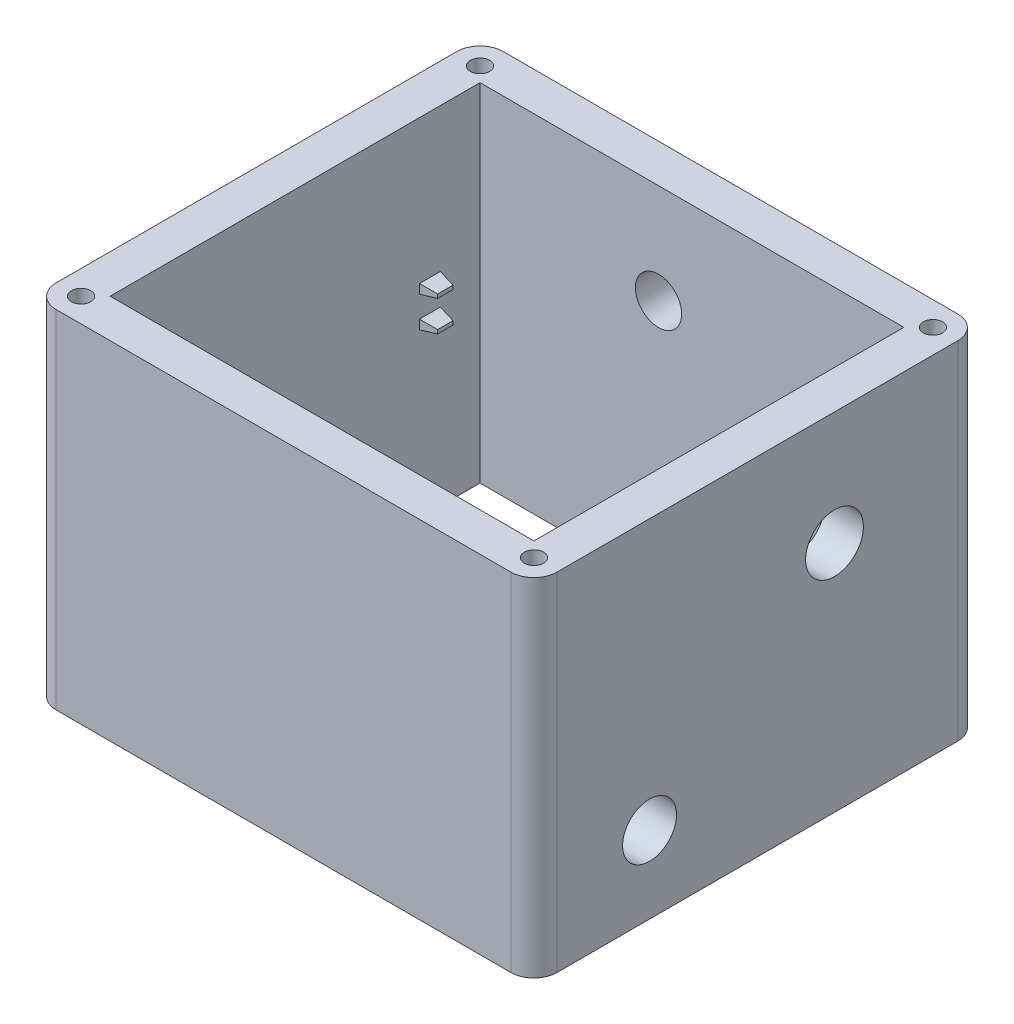
SolidWorks part; units mm, degrees
material "ABS PC"
ref_plane "Front Plane" through (0, 0, 0) normal (0, 0, 1) x (1, 0, 0)
ref_plane "Top Plane" through (0, 0, 0) normal (0, 1, 0) x (1, 0, 0)
ref_plane "Right Plane" through (0, 0, 0) normal (1, 0, 0) x (0, 0, -1)
sketch "Base Sketch" plane through (0, 0, 0) normal (0, 1, 0) x (1, 0, 0)
  line L1 (0, 0) -> (65, 0)
  line L2 (0, 0) -> (0, 58)
  line L3 (0, 58) -> (65, 58)
  line L4 (65, 0) -> (65, 58)
  line L5 (5, 53) -> (60, 53)
  line L6 (5, 53) -> (5, 5)
  line L7 (5, 5) -> (60, 5)
  line L8 (60, 53) -> (60, 5)
  line L9 (5, 48) -> (7, 48)
  line L10 (5, 48) -> (5, 45)
  line L11 (5, 45) -> (7, 45)
  line L12 (7, 48) -> (7, 45)
  line L17 (44, 5) -> (47, 5)
  line L18 (44, 5) -> (44, 7)
  line L19 (44, 7) -> (47, 7)
  line L20 (47, 5) -> (47, 7)
  line L21 (60, 30) -> (58, 30)
  line L22 (60, 30) -> (60, 33)
  line L23 (60, 33) -> (58, 33)
  line L24 (58, 30) -> (58, 33)
  point P9 (32.5, 58)
  point P10 (32.5, 53)
  point P11 (0, 29)
  point P12 (5, 29)
  point P25 (47, 6)
  point P26 (6, 45)
  point P27 (59, 33)
  point P28 (6, 48)
  point P29 (44, 6)
  dimension "D1" = 65
  dimension "D2" = 55
  dimension "D3" = 58
  dimension "D4" = 48
  dimension "D5" = 5
  dimension "D6" = 3
  dimension "D7" = 2
  dimension "D8" = 3
  dimension "D9" = 3
  dimension "D10" = 2
  dimension "D11" = 13
  dimension "D12" = 2
  dimension "D13" = 20
  dimension "D14" = 53
  dimension "D15" = 42
extrude "Walls" add sketch "Base Sketch" along normal blind 45 contours L1 L4 L3 L2 L5 L8 L7 L6 region at (0.8711, 0, -29)
extrude "Clips Top" add sketch "Sketch<8>" along normal blind 1.5 from offset 25 contours L12 L9 L6 L11 | L24 L21 L8 L23 | L7 L20 L19 L18 region at (6, 0, -46.5) region at (59, 0, -31.5) region at (45.5, 0, -6)
sketch "Sketch<8>" plane through (0, 0, 0) normal (0, 1, 0) x (1, 0, 0) same geometry as "Base Sketch"
extrude "Clips Bottom" add sketch "Sketch<10>" along normal blind 1.5 from offset 21 contours L12 L9 L6 L11 | L24 L21 L8 L23 | L7 L20 L19 L18 region at (6, 0, -46.5) region at (59, 0, -31.5) region at (45.5, 0, -6)
sketch "Sketch<10>" plane through (0, 0, 0) normal (0, 1, 0) x (1, 0, 0) same geometry as "Base Sketch"
chamfer "Chamfer5" distance 0.5 angle 80 4 edges at (58, 25.75, -33) (58, 26.5, -31.5) (58, 25.75, -30) (58, 25, -31.5) first distance on face at (58, 25.75, -31.5)
chamfer "Chamfer6" distance 0.5 angle 80 4 edges at (47, 25.75, -7) (45.5, 26.5, -7) (44, 25.75, -7) (45.5, 25, -7) first distance on face at (45.5, 25.75, -7)
chamfer "Chamfer4" distance 0.5 angle 80 4 edges at (7, 25.75, -45) (7, 26.5, -46.5) (7, 25.75, -48) (7, 25, -46.5) first distance on face at (7, 25.75, -46.5)
chamfer "Chamfer7" distance 0.5 angle 80 4 edges at (7, 21.75, -45) (7, 22.5, -46.5) (7, 21.75, -48) (7, 21, -46.5) first distance on face at (7, 21.75, -46.5)
chamfer "Chamfer8" distance 0.5 angle 80 4 edges at (58, 21.75, -33) (58, 22.5, -31.5) (58, 21.75, -30) (58, 21, -31.5) first distance on face at (58, 21.75, -31.5)
chamfer "Chamfer9" distance 0.5 angle 80 4 edges at (47, 21.75, -7) (45.5, 22.5, -7) (44, 21.75, -7) (45.5, 21, -7) first distance on face at (45.5, 21.75, -7)
sketch "Jack & Encoder" plane through (0, 0, 0) normal (1, 0, 0) x (0, 0, -1)
  line L0 (0, 0) -> (58, 0) construction
  line L1 (53, 45) -> (53, 0) construction
  line L2 (5, 45) -> (5, 0) construction
  line L3 (5, 25.1473) -> (7, 25.5) construction
  line L4 (7, 25.75) -> (7, 21.75) construction
  line L5 (7, 26) -> (7, 25.5) construction
  line L6 (7, 22) -> (7, 21.5) construction
  circle A0 centre (15, 10) radius 3.5
  circle A1 centre (39, 30.25) radius 3.75
  point P16 (6, 25.3237)
  point P23 (7, 23.75)
  dimension "D1" = 7
  dimension "D5" = 7.5
  dimension "D2" = 10
  dimension "D3" = 10
  dimension "D4" = 38
  dimension "D6" = 33
  dimension "D7" = 6.5
extrude "Right Holes" cut sketch "Jack & Encoder" against normal blind 23 from offset 70 contours A0 | A1
sketch "Holes" plane through (0, 0, 0) normal (0, 1, 0) x (1, 0, 0)
  line L0 (5, 53) -> (0, 58) construction
  line L1 (60, 53) -> (65, 58) construction
  line L2 (60, 5) -> (65, 0) construction
  line L3 (0, 0) -> (5, 5) construction
  line L4 (3.1155, 54.8845) -> (65, 54.8845) construction
  line L5 (65, 0) -> (65, 58) construction
  line L6 (61.8845, 54.8845) -> (61.8845, 0) construction
  line L7 (0, 0) -> (65, 0) construction
  line L8 (61.8845, 3.1155) -> (0, 3.1155) construction
  line L9 (0, 0) -> (0, 58) construction
  circle A0 centre (3.1155, 54.8845) radius 1.25
  circle A1 centre (61.8845, 54.8845) radius 1.25
  circle A2 centre (61.8845, 3.1155) radius 1.25
  circle A3 centre (3.1155, 3.1155) radius 1.25
  point P12 (0, 0)
  point P25 (3.1155, 3.1155)
  point P29 (3.1155, 3.1155)
  point P33 (2.5, 55.5)
  dimension "D1" = 2.5
  dimension "D2" = 2.5
  dimension "D3" = 2.5
  dimension "D4" = 2.5
fillet "Fillet1" radius 3 4 edges at (65, 22.5, -58) (0, 22.5, -58) (0, 22.5, 0) (65, 22.5, 0)
extrude "Mounting Holes" cut sketch "Holes" along normal through all
sketch "On-off Switch" plane through (0, 0, 0) normal (0, 0, 1) x (1, 0, 0)
  circle A0 centre (28.1644, 32.056) radius 3
  circle A17 centre (8.0644, 30.9889) radius 0.8
  circle A18 centre (8.0644, 33.4889) radius 0.8
  circle A19 centre (10.5644, 28.4889) radius 0.8
  circle A20 centre (10.5644, 33.4889) radius 0.8
  circle A21 centre (15.6644, 30.9889) radius 0.8
  circle A22 centre (18.1644, 28.4889) radius 0.8
  circle A23 centre (18.1644, 33.4889) radius 0.8
  circle A24 centre (55.8644, 33.0797) radius 0.8
  circle A25 centre (38.1644, 33.0797) radius 0.8
  circle A26 centre (40.6644, 33.0797) radius 0.8
  circle A27 centre (40.6644, 30.5797) radius 0.8
  circle A28 centre (45.7644, 33.0797) radius 0.8
  circle A29 centre (48.2644, 33.0797) radius 0.8
  circle A30 centre (48.2644, 30.5797) radius 0.8
  circle A31 centre (55.8644, 28.0797) radius 0.8
  circle A32 centre (53.3644, 30.5797) radius 0.8
  point P2 (0, 0)
  point P3 (0, 0)
  point P4 (0, 0)
  point P5 (0, 0)
  point P6 (0, 0)
  point P7 (0, 0)
  point P9 (0, 0)
  point P10 (0, 0)
  point P11 (0, 0)
  point P12 (37.8097, 29.9359)
  point P17 (0, 0)
  point P26 (0, 0)
  point P27 (0, 0)
  point P28 (0, 0)
  point P29 (37.8914, 29.6157)
  point P30 (0, 0)
  point P31 (39.7123, 30.2834)
  point P32 (32.3123, 32.7394)
  point P35 (0, 0)
  point P36 (0, 0)
  point P37 (0, 0)
  point P38 (0, 0)
  point P39 (0, 0)
  point P40 (0, 0)
  point P41 (17.991, 33.5664)
  point P45 (0, 0)
  point P46 (0, 0)
  point P47 (0, 0)
  point P48 (37.7293, 32.0809)
  point P49 (0, 0)
  point P50 (0, 0)
  point P57 (0, 0)
  point P58 (0, 0)
  point P59 (0, 0)
  point P60 (0, 0)
  point P61 (45.4522, 31.9443)
  point P68 (0, 0)
  point P69 (0, 0)
  point P83 (0, 0)
  point P84 (0, 0)
  point P85 (0, 0)
  point P86 (0, 0)
  point P87 (0, 0)
  point P88 (-7.4243, 26.6793)
  dimension "D1" = 6
  dimension "D2" = 1.6
  dimension "D3" = 1.6
  dimension "D4" = 1.6
  dimension "D5" = 1.6
  dimension "D6" = 1.6
  dimension "D7" = 1.6
  dimension "D8" = 1.6
  dimension "D9" = 1.6
  dimension "D10" = 1.6
  dimension "D11" = 1.6
  dimension "D12" = 1.6
  dimension "D13" = 1.6
  dimension "D14" = 1.6
  dimension "D15" = 1.6
  dimension "D16" = 1.6
  dimension "D17" = 1.6
  dimension "D18" = 2.5
  dimension "D19" = 2.5
  dimension "D20" = 2.5
  dimension "D21" = 7.6
  dimension "D22" = 7.6
  dimension "D23" = 2.5
  dimension "D24" = 2.5
  dimension "D25" = 2.5
  dimension "D26" = 2.5
  dimension "D27" = 2.5
  dimension "D28" = 2.5
  dimension "D29" = 2.5
  dimension "D30" = 2.5
  dimension "D31" = 2.5
  dimension "D32" = 7.6
  dimension "D33" = 2.5
  dimension "D34" = 2.5
  dimension "D35" = 2.5
  dimension "D36" = 2.5
  dimension "D37" = 2.5
  dimension "D38" = 10
  dimension "D39" = 10
extrude "On-off toggle switch hole" cut sketch "On-off Switch" against normal blind 13 from offset 50 contours A0 offset against normal yes
extrude "Boss-Extrude7" add sketch "On-off Switch<7>" against normal blind 0.9 from surface contours A26 | A29 | A25 | A27 | A28 | A24 | A18 | A23 | A26 | A24 | A25 | A17 | A19 | A21 | A22 | A27 | A28 | A29 | A30 | A32 | A31 region at (8.0644, 33.4889, 0) region at (18.1644, 33.4889, 0) region at (55.8644, 33.0797, 0) region at (40.6644, 33.0797, 0) starting at face at (25.1644, 32.056, -58)
sketch "On-off Switch<7>" plane through (0, 0, 0) normal (0, 0, 1) x (1, 0, 0) same geometry as "On-off Switch"
equation "\"D39@On-off Switch\"=\"D38@On-off Switch\""
